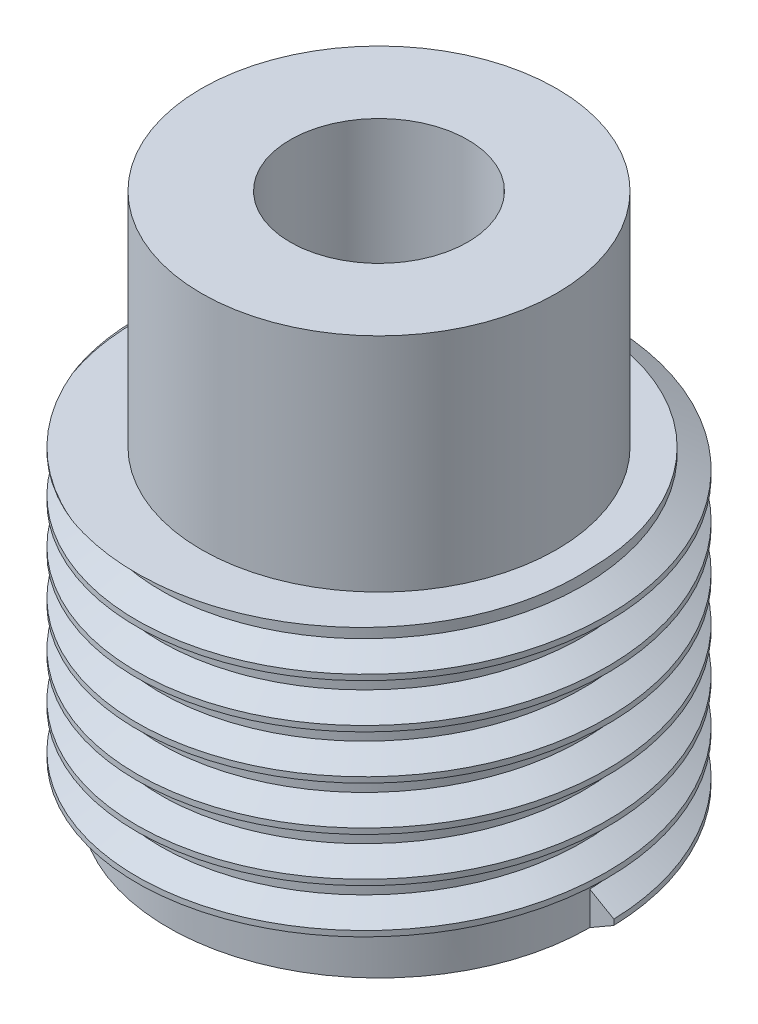
SolidWorks part; units mm, degrees
ref_plane "Alzado" through (0, 0, 0) normal (0, 0, 1) x (1, 0, 0)
ref_plane "Planta" through (0, 0, 0) normal (0, 1, 0) x (1, 0, 0)
ref_plane "Vista lateral" through (0, 0, 0) normal (1, 0, 0) x (0, 0, -1)
sketch "Croquis1" plane through (0, 0, 0) normal (0, 1, 0) x (1, 0, 0)
  circle A0 centre (0, 0) radius 9.5
  dimension "D1" = 19
extrude "Saliente-Extruir1" add sketch "Croquis1" along normal blind 14
sketch "Croquis2" plane through (0, 14, 0) normal (0, 1, 0) x (1, 0, 0)
  circle A0 centre (0, 0) radius 8
  dimension "D1" = 16
extrude "Saliente-Extruir2" add sketch "Croquis2" along normal blind 10
sketch "Croquis3" plane through (0, 24, 0) normal (0, 1, 0) x (1, 0, 0)
  circle A0 centre (0, 0) radius 4
  dimension "D1" = 8
extrude "Cortar-Extruir1" cut sketch "Croquis3" against normal blind 28
thread "Rosca1" pitch 2 method extrude profile "Perfil de rosca1" start angle 0, offset 0, length 0, pitch 2, diameter 19
ref_plane "Plano1" through (9.5, 0, 0) normal (0, 0, 1) x (1, 0, 0)
sketch "Perfil de rosca1" plane through (9.5, 0, 0) normal (0, 0, 1) x (1, 0, 0)
  line L0 (0, 0) -> (0, 2) construction
  line L1 (0, 0) -> (1.0825, 0.625)
  line L2 (1.0825, 0.625) -> (1.0825, 0.875)
  line L3 (1.0825, 0.875) -> (0, 1.5)
  line L4 (1.0825, 0.75) -> (0, 0.75) construction
  line L11 (0, 0) -> (0, 1.5)
  point P2 (0, 0)
  dimension "Pitch" = 2
  dimension "Profile_Angle" = 60
  dimension "Profile_Land" = 0.25
  dimension "Profile_Height" = 1.0825
sketch "Croquis6" plane through (0, 14, 0) normal (0, 1, 0) x (1, 0, 0)
  circle A0 centre (0, 0) radius 12.5
  circle A2 centre (0, 0) radius 8 construction
  circle A3 centre (0, 0) radius 8
  dimension "D1" = 25
extrude "Cortar-Extruir2" cut sketch "Croquis6" along normal blind 28
sketch "Croquis7" plane through (0, 0, 0) normal (0, -1, 0) x (1, 0, 0)
  line L0 (0, 9.5) -> (0, -9.5) construction
  circle A0 centre (0, 0) radius 9.5 construction
  circle A1 centre (0, 0) radius 9.5 construction
  circle A2 centre (0, 7) radius 2
  circle A3 centre (0, -7) radius 2
  dimension "D1" = 4
  dimension "D2" = 4
  dimension "D3" = 7
  dimension "D4" = 7
extrude "Cortar-Extruir3" cut sketch "Croquis7" against normal blind 3
